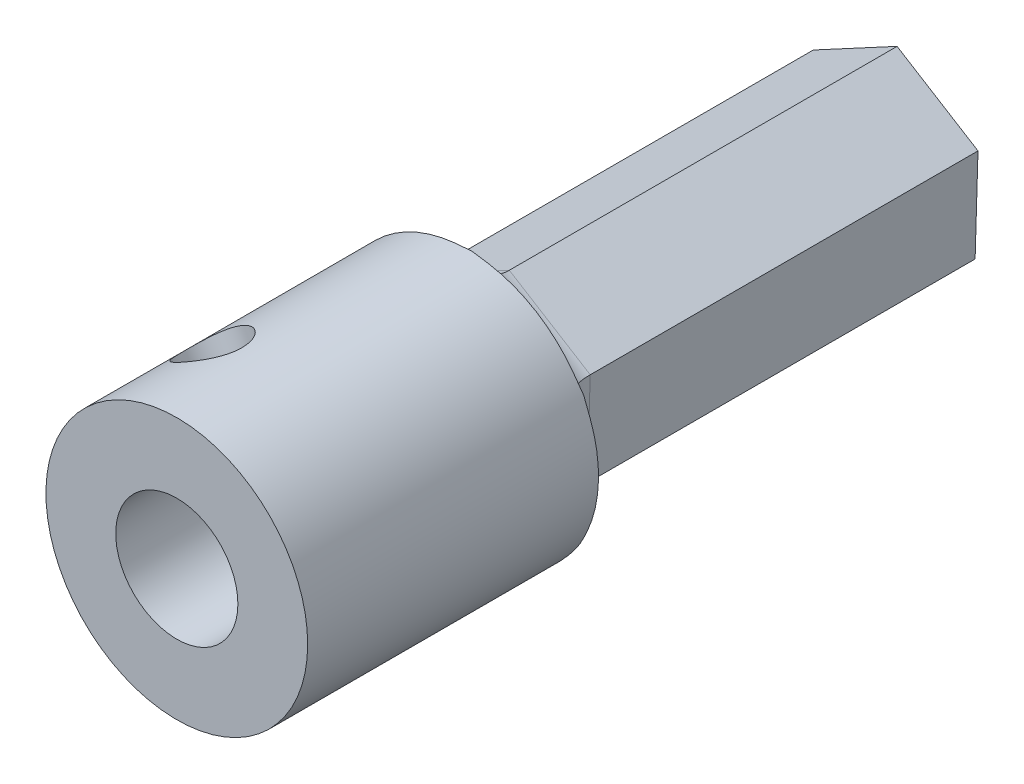
SolidWorks part; units mm, degrees
ref_plane "Front Plane" through (0, 0, 0) normal (0, 0, 1) x (1, 0, 0)
ref_plane "Top Plane" through (0, 0, 0) normal (0, 1, 0) x (1, 0, 0)
ref_plane "Right Plane" through (0, 0, 0) normal (1, 0, 0) x (0, 0, -1)
sketch "Sketch1" plane through (0, 0, 0) normal (0, 0, 1) x (1, 0, 0)
  line L1 (4.3226, 2.3236) -> (0.149, 4.9052)
  line L2 (0.149, 4.9052) -> (-4.1735, 2.5817)
  line L3 (-4.1735, 2.5817) -> (-4.3226, -2.3236)
  line L4 (-4.3226, -2.3236) -> (-0.149, -4.9052)
  line L5 (-0.149, -4.9052) -> (4.1735, -2.5817)
  line L6 (4.1735, -2.5817) -> (4.3226, 2.3236)
  circle A0 centre (0, 0) radius 4.25 construction
  point P1 (0, 0)
  dimension "D1" = 8.5
extrude "Boss-Extrude1" add sketch "Sketch1" along normal blind 22 contours L2 L3 L4 L5 L6 L1
sketch "Sketch2" plane through (0, 0, 22) normal (0, 0, 1) x (1, 0, 0)
  circle A0 centre (0, 0) radius 6.75
  dimension "D1" = 13.5
extrude "Boss-Extrude2" add sketch "Sketch2" along normal blind 15 contours A0
sketch "Sketch3" plane through (0, 0, 37) normal (0, 0, 1) x (1, 0, 0)
  circle A0 centre (0, 0) radius 3.15
  dimension "D1" = 6.3
extrude "Cut-Extrude1" cut sketch "Sketch3" against normal blind 13
fillet "Fillet2" radius 2 6 edges at (2.0123, -3.7434, 22) (4.248, -0.1291, 22) (2.2358, 3.6144, 22) (-2.0123, 3.7434, 22) (-4.248, 0.1291, 22) (-2.2358, -3.6144, 22)
sketch "Sketch8" plane through (2.0123, -3.7434, 0) normal (0.4735, -0.8808, 0) x (-0.8808, -0.4735, 0)
  line L1 (-6.75, -37) -> (6.75, -37) construction
  circle A0 centre (0, -32) radius 1.65
  dimension "D1" = 3.3
  dimension "D2" = 5
extrude "Cut-Extrude2" cut sketch "Sketch8" against normal blind 15 and the other way blind 15
sketch "Sketch9" plane through (0, 0, 0) normal (0, 0, -1) x (-1, 0, 0)
  circle A0 centre (0, 0) radius 1.65
  dimension "D1" = 3.3
extrude "Cut-Extrude3" cut sketch "Sketch9" against normal blind 25
